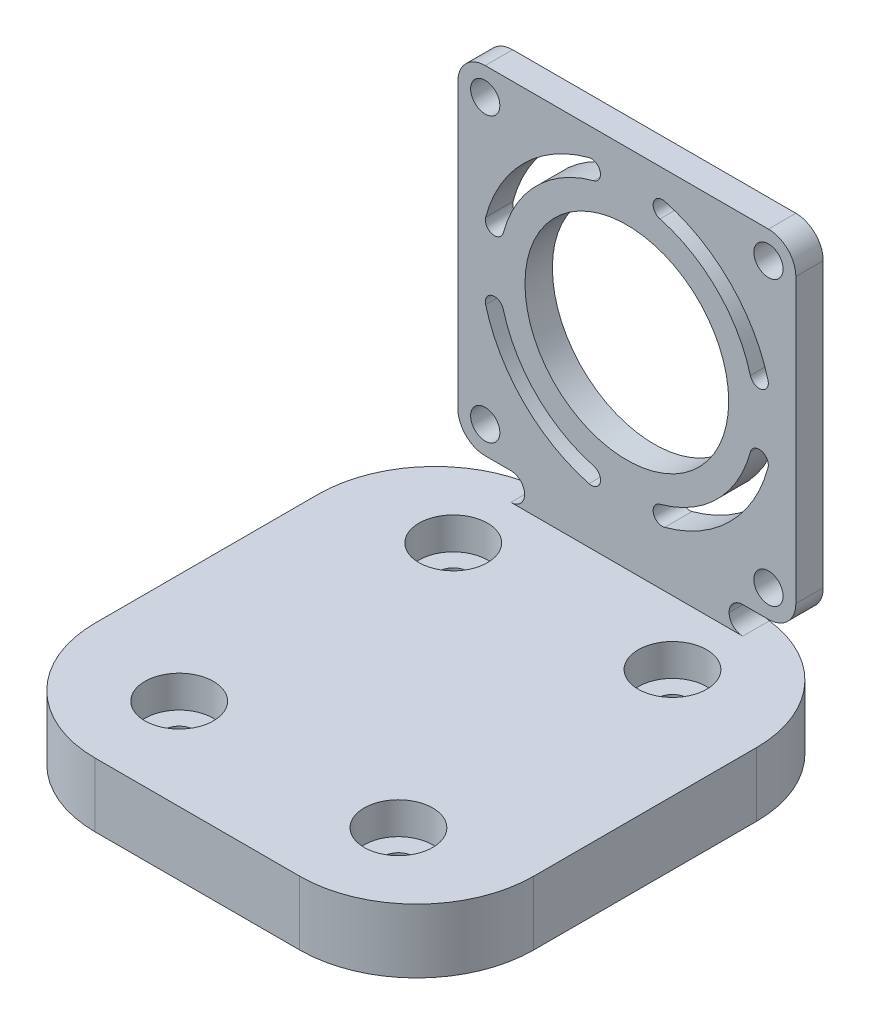
SolidWorks part; units mm, degrees
ref_plane "前基準面" through (0, 0, 0) normal (0, 0, 1) x (1, 0, 0)
ref_plane "上基準面" through (0, 0, 0) normal (0, 1, 0) x (1, 0, 0)
ref_plane "右基準面" through (0, 0, 0) normal (1, 0, 0) x (0, 0, -1)
sketch "草圖1" plane through (0, 0, 0) normal (0, 1, 0) x (1, 0, 0)
  line L0 (-12, 0) -> (12, 0)
  line L1 (-12, 15) -> (12, 15)
  line L2 (-12, 15) -> (-12, -15)
  line L3 (-12, -15) -> (12, -15)
  line L4 (12, 15) -> (12, -15)
  line L6 (-24, -25) -> (24, -25)
  line L7 (-24, -25) -> (-24, 25)
  line L8 (-24, 25) -> (24, 25)
  line L9 (24, -25) -> (24, 25)
  line L10 (-24, -25) -> (24, 25) construction
  line L11 (-24, 25) -> (24, -25) construction
  circle A0 centre (-12, 15) radius 1.6
  circle A1 centre (12, 15) radius 1.6
  circle A2 centre (12, -15) radius 1.6
  circle A3 centre (-12, -15) radius 1.6
  point P7 (0, 0)
  point P12 (0, 0)
  dimension "D3" = 3.2
  dimension "D1" = 24
  dimension "D2" = 30
  dimension "D4" = 48
  dimension "D5" = 50
extrude "填料-伸長1" add sketch "草圖1" along normal blind 7 contours A1 L1 A0 L2 L0 L4 | A3 L3 A2 L4 L0 L2 | L6 L9 L8 L7 A3 L2 A0 L1 A1 L4 A2 L3 region at (0, 0, -7.4229) region at (0, 0, 7.4229) region at (-23.3069, 0, 0)
sketch "草圖4" plane through (0, 7, 0) normal (0, 1, 0) x (1, 0, 0)
  circle A0 centre (-12, 15) radius 3.75
  circle A1 centre (12, 15) radius 3.75
  circle A2 centre (12, -15) radius 3.75
  circle A3 centre (-12, -15) radius 3.75
  dimension "D1" = 7.5
extrude "除料-伸長1" cut sketch "草圖4" against normal blind 3.5
fillet "圓角1" radius 12.81 4 edges at (24, 3.5, 25) (24, 3.5, -25) (-24, 3.5, -25) (-24, 3.5, 25)
sketch "草圖5" plane through (0, 0, -25) normal (0, 0, -1) x (-1, 0, 0)
  line L0 (0, 44) -> (0, 13)
  line L1 (11.19, 7) -> (-11.19, 7)
  line L2 (11.19, 7) -> (11.19, 13)
  line L3 (11.19, 13) -> (-11.19, 13)
  line L4 (-11.19, 7) -> (-11.19, 13)
  line L5 (-15.5, 44) -> (15.5, 44)
  line L6 (-15.5, 44) -> (-15.5, 13)
  line L7 (-15.5, 13) -> (15.5, 13)
  line L8 (15.5, 44) -> (15.5, 13)
  line L9 (0, 28.5) -> (3.8823, 42.9889)
  line L14 (0, 28.5) -> (14.4889, 32.3823)
  line L16 (-18.5, 10) -> (18.5, 10)
  line L17 (-18.5, 10) -> (-18.5, 47)
  line L18 (-18.5, 47) -> (18.5, 47)
  line L19 (18.5, 10) -> (18.5, 47)
  line L20 (-18.5, 10) -> (18.5, 47) construction
  line L21 (-18.5, 47) -> (18.5, 10) construction
  circle A0 centre (15.5, 44) radius 1.6
  circle A1 centre (-15.5, 44) radius 1.6
  circle A2 centre (15.5, 13) radius 1.6
  circle A3 centre (-15.5, 13) radius 1.6
  circle A4 centre (-15.5, 44) radius 3
  circle A5 centre (15.5, 44) radius 3
  circle A6 centre (15.5, 13) radius 3
  circle A7 centre (-15.5, 13) radius 3
  circle A8 centre (0, 28.5) radius 11.15
  arc A9 (3.8823, 42.9889) -> (14.4889, 32.3823) centre (0, 28.5) cw construction
  arc A10 (15.4548, 32.6411) -> (4.1411, 43.9548) centre (0, 28.5) ccw
  arc A11 (13.523, 32.1235) -> (3.6235, 42.023) centre (0, 28.5) ccw
  arc A12 (13.523, 32.1235) -> (15.4548, 32.6411) centre (14.4889, 32.3823) ccw
  arc A13 (4.1411, 43.9548) -> (3.6235, 42.023) centre (3.8823, 42.9889) ccw
  arc A14 (-3.6235, 42.023) -> (-13.523, 32.1235) centre (0, 28.5) ccw
  arc A15 (-3.6235, 42.023) -> (-4.1411, 43.9548) centre (-3.8823, 42.9889) ccw
  arc A16 (-15.4548, 32.6411) -> (-13.523, 32.1235) centre (-14.4889, 32.3823) ccw
  arc A17 (-4.1411, 43.9548) -> (-15.4548, 32.6411) centre (0, 28.5) ccw
  arc A18 (-14.4889, 32.3823) -> (-3.8823, 42.9889) centre (0, 28.5) cw construction
  arc A19 (-13.523, 24.8765) -> (-3.6235, 14.977) centre (0, 28.5) ccw
  arc A20 (-13.523, 24.8765) -> (-15.4548, 24.3589) centre (-14.4889, 24.6177) ccw
  arc A21 (-4.1411, 13.0452) -> (-3.6235, 14.977) centre (-3.8823, 14.0111) ccw
  arc A22 (-15.4548, 24.3589) -> (-4.1411, 13.0452) centre (0, 28.5) ccw
  arc A23 (-3.8823, 14.0111) -> (-14.4889, 24.6177) centre (0, 28.5) cw construction
  arc A24 (3.6235, 14.977) -> (13.523, 24.8765) centre (0, 28.5) ccw
  arc A25 (3.6235, 14.977) -> (4.1411, 13.0452) centre (3.8823, 14.0111) ccw
  arc A26 (15.4548, 24.3589) -> (13.523, 24.8765) centre (14.4889, 24.6177) ccw
  arc A27 (4.1411, 13.0452) -> (15.4548, 24.3589) centre (0, 28.5) ccw
  arc A28 (14.4889, 24.6177) -> (3.8823, 14.0111) centre (0, 28.5) cw construction
  point P14 (0, 13)
  point P17 (0, 28.5)
  point P26 (0, 28.5)
  point P31 (10.6066, 39.1066)
  point P42 (-10.6066, 39.1066)
  point P49 (-10.6066, 17.8934)
  point P56 (10.6066, 17.8934)
  point P61 (0, 28.5)
  line M5 (11.19, 7) -> (-11.19, 7)
  dimension "D2" = 3.2
  dimension "D7" = 6
  dimension "D5" = 22.3
  dimension "D10" = 1
  dimension "D1" = 6
  dimension "D3" = 31
  dimension "D4" = 31
  dimension "D6" = 60
  dimension "D8" = 15
  dimension "D9" = 15
  dimension "D11" = 4
extrude "填料-伸長2" add sketch "草圖5" against normal blind 3 contours A6 L8 A5 L5 L0 L3 L7 | A7 L7 L3 L0 L5 A4 L6 | L4 L16 L2 L3 | L16 L4 L2 M5 | A6 L7 L2 L16 | A6 L8 A2 L7 | L8 A6 L7 A2 | A6 L19 A5 L8 | A5 L5 A0 L8 | L5 A5 L8 A0 | A5 L18 A4 L5 | L5 A4 L6 A1 | L6 A4 L5 A1 | A7 L6 A4 L17 | L7 A7 L6 A3 | L6 A7 L7 A3 | A7 L16 L4 L7 | L14 A11 L9 A8 region at (-6.25, 43.6534, -25) region at (0.3466, 41.825, -25) region at (0, 45.5406, -25) region at (13.9906, 42.4906, -25) region at (13.2, 44.0849, -25) region at (-13.4387, 46.0613, -25) region at (-13.9906, 42.4906, -25) region at (-8.5275, 37.0275, -25) region at (17.0406, 28.5, -25) region at (-17.0406, 28.5, -25) region at (0, 11.5, -25) region at (13.9906, 14.5094, -25) region at (15.5849, 15.3, -25) region at (-17.5613, 15.0613, -25) region at (-13.9906, 14.5094, -25) region at (-12.2816, 11.2265, -25) region at (12.2816, 11.2265, -25) region at (0, 8.5, -25)
fillet "圓角2" radius 1.5 4 edges at (11.19, 7, -23.5) (11.19, 10, -23.5) (-11.19, 7, -23.5) (-11.19, 10, -23.5)
